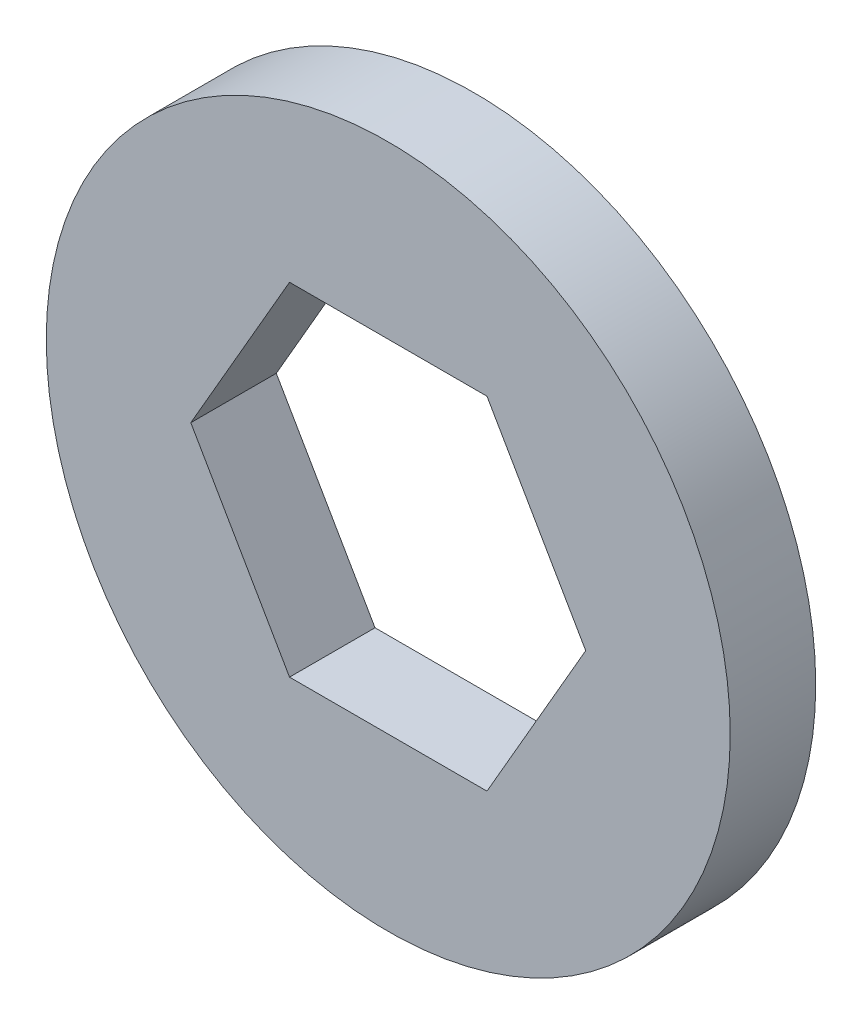
SolidWorks part; units mm, degrees
ref_plane "Front Plane" through (0, 0, 0) normal (0, 0, 1) x (1, 0, 0)
ref_plane "Top Plane" through (0, 0, 0) normal (0, 1, 0) x (1, 0, 0)
ref_plane "Right Plane" through (0, 0, 0) normal (1, 0, 0) x (0, 0, -1)
sketch "Sketch1" plane through (0, 0, 0) normal (0, 0, 1) x (1, 0, 0)
  line L1 (-7.3323, 0) -> (-3.6662, -6.35)
  line L2 (-3.6662, -6.35) -> (3.6662, -6.35)
  line L3 (3.6662, -6.35) -> (7.3323, 0)
  line L4 (7.3323, 0) -> (3.6662, 6.35)
  line L5 (3.6662, 6.35) -> (-3.6662, 6.35)
  line L6 (-3.6662, 6.35) -> (-7.3323, 0)
  circle A0 centre (0, 0) radius 6.35 construction
  circle A1 centre (0, 0) radius 12.7
  dimension "D2" = 25.4
  dimension "D1" = 12.7
extrude "Boss-Extrude1" add sketch "Sketch1" along normal blind 3.175
ref_axis "Axis1" through (0, 0, -2.5954) along (0, 0, 1)
